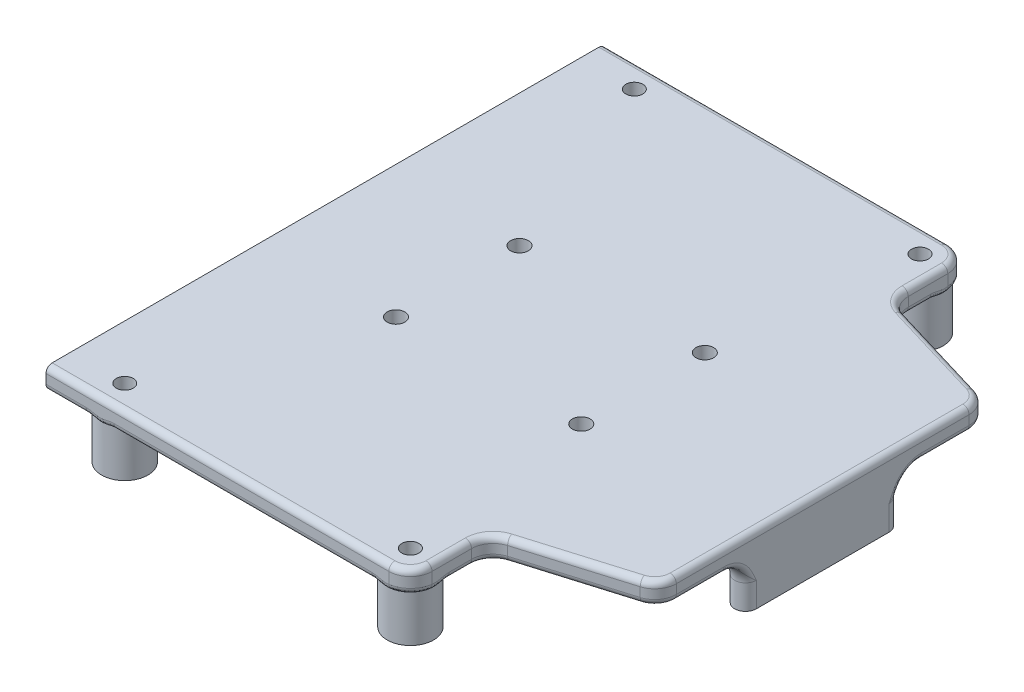
SolidWorks part; units mm, degrees
ref_plane "Front Plane" through (0, 0, 0) normal (0, 0, 1) x (1, 0, 0)
ref_plane "Top Plane" through (0, 0, 0) normal (0, 1, 0) x (1, 0, 0)
ref_plane "Right Plane" through (0, 0, 0) normal (1, 0, 0) x (0, 0, -1)
sketch "Sketch2" plane through (0, 0, 0) normal (0, 1, 0) x (1, 0, 0)
  line L0 (0, -90.5) -> (0, 90.5)
  line L1 (0, 90.5) -> (118, 90.5)
  line L3 (161, 52.5994) -> (161, -52.5994)
  line L5 (118, -90.5) -> (0, -90.5)
  line L6 (118, -90.5) -> (118, -65.5)
  line L7 (118, -65.5) -> (161, -52.5994)
  line L8 (118, 90.5) -> (118, 65.5)
  line L9 (118, 65.5) -> (161, 52.5994)
  circle A0 centre (17.5, -82.5) radius 2.75
  circle A1 centre (110, -82.5) radius 2.75
  circle A2 centre (17.5, 82.5) radius 2.75
  circle A3 centre (110, 82.5) radius 2.75
  point P3 (0, 0)
  point P8 (161, 0)
  dimension "D5" = 5.5
  dimension "D8" = 92.5
  dimension "D9" = 8
  dimension "D1" = 181
  dimension "D2" = 118
  dimension "D3" = 43
  dimension "D4" = 163.3
  dimension "D6" = 8
  dimension "D7" = 17.5
  dimension "D10" = 25
extrude "Boss-Extrude1" add sketch "Sketch2" along normal blind 7
fillet "Fillet1" radius 7 6 edges at (118, 3.5, -90.5) (118, 3.5, -65.5) (161, 3.5, -52.5994) (161, 3.5, 52.5994) (118, 3.5, 65.5) (118, 3.5, 90.5)
sketch "Sketch3" plane through (0, 0, 0) normal (0, -1, 0) x (1, 0, 0)
  line L0 (161, 47.3912) -> (161, -47.3912) construction
  line L1 (161, 25) -> (154, 25)
  line L2 (161, 25) -> (161, -25)
  line L3 (161, -25) -> (154, -25)
  line L4 (154, 25) -> (154, -25)
  circle A0 centre (17.5, 82.5) radius 2.75
  circle A1 centre (17.5, 82.5) radius 7.5
  circle A2 centre (110, 82.5) radius 2.75
  circle A3 centre (110, 82.5) radius 7.5
  circle A4 centre (110, -82.5) radius 2.75
  circle A5 centre (110, -82.5) radius 7.5
  circle A6 centre (17.5, -82.5) radius 2.75
  circle A7 centre (17.5, -82.5) radius 7.5
  point P6 (161, 0)
  dimension "D3" = 5.5
  dimension "D4" = 15
  dimension "D1" = 7
  dimension "D2" = 50
extrude "Boss-Extrude2" add sketch "Sketch3" along normal blind 15
fillet "Fillet2" 2 edges at (161, -7.5, -25) (154, -7.5, -25) type full round first side face at (161, -2, 0) second side face at (154, -7.5, 0) middle face at (157.5, -7.5, -25)
fillet "Fillet3" 2 edges at (161, -7.5, 25) (154, -7.5, 25) type full round first side face at (161, -2, 0.875) second side face at (154, -7.5, 1.75) middle face at (157.5, -7.5, 25)
fillet "Fillet4" radius 7 3 edges at (157.5, 0, 25) (157.5, 0, -25) (154, 0, 0)
fillet "Fillet5" radius 2 27 edges at (161, -1.6915, -26.2957) (55.5, 0, -90.5) (55.5, 0, 90.5) (161, -1.6915, 26.2957) (55.5, 7, 90.5) (55.5, 7, -90.5) (161, 0, -39.3954) (161, 0, 39.3954) (161, 7, 0) (118, 0, -77.1041) (119.3839, 0, -66.5297) (139.5, 0, -59.0497) (159.6161, 0, -51.5697) (118, 0, 77.1041) (119.3839, 0, 66.5297) (139.5, 0, 59.0497) (159.6161, 0, 51.5697) (115.9497, 7, 88.4497) (118, 7, 77.1041) (119.3839, 7, 66.5297) (139.5, 7, 59.0497) (159.6161, 7, 51.5697) (115.9497, 7, -88.4497) (118, 7, -77.1041) (119.3839, 7, -66.5297) (139.5, 7, -59.0497) (159.6161, 7, -51.5697)
sketch "Sketch4" plane through (0, 7, 0) normal (0, 1, 0) x (1, 0, 0)
  line L0 (161, 47.3912) -> (161, -47.3912) construction
  circle A0 centre (102.82, 20) radius 2.87
  circle A1 centre (102.82, -20) radius 2.87
  circle A2 centre (42.82, -20) radius 2.87
  circle A3 centre (42.82, 20) radius 2.87
  dimension "D1" = 58.18
  dimension "D4" = 5.74
  dimension "D2" = 40
  dimension "D3" = 60
  dimension "D5" = 20
extrude "Cut-Extrude1" cut sketch "Sketch4" against normal up to surface (7 mm away) up to face at (100.5717, 0, 0)
